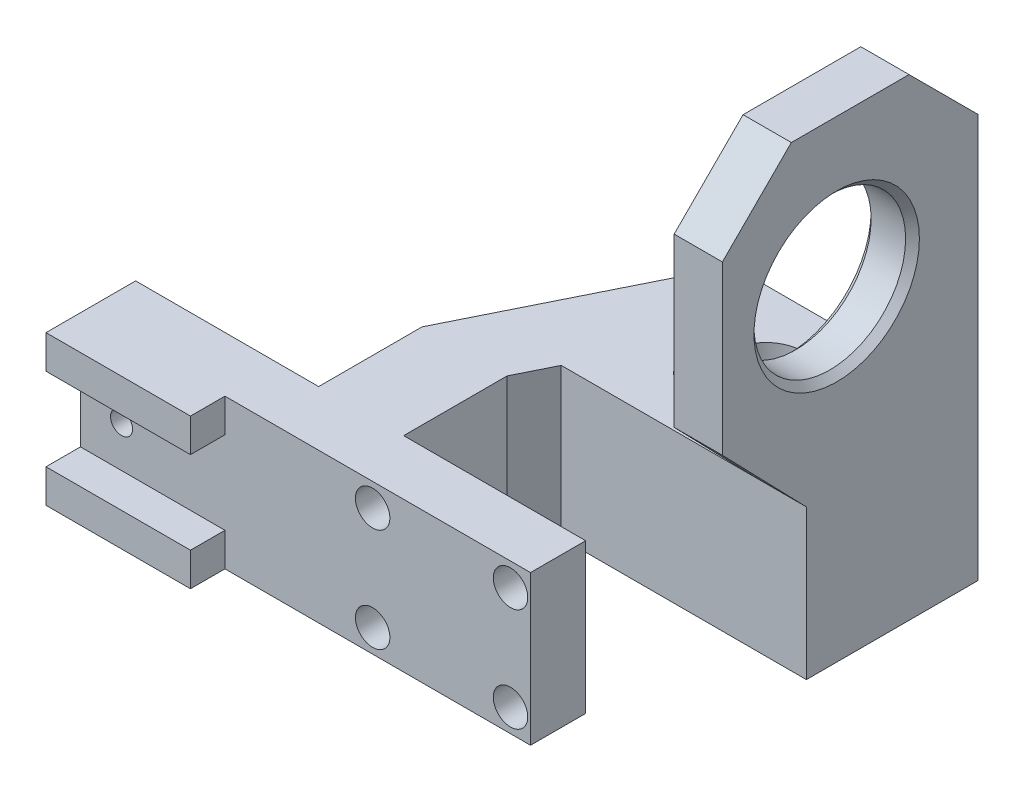
SolidWorks part; units mm, degrees
ref_plane "Přední rovina" through (0, 0, 0) normal (0, 0, 1) x (1, 0, 0)
ref_plane "Horní rovina" through (0, 0, 0) normal (0, 1, 0) x (1, 0, 0)
ref_plane "Pravá rovina" through (0, 0, 0) normal (1, 0, 0) x (0, 0, -1)
sketch "Skica1" plane through (0, 0, 0) normal (0, 0, 1) x (1, 0, 0)
  line L1 (16.212, -19.9414) -> (-34.0669, -19.9414)
  line L2 (16.212, -19.9414) -> (16.212, 1.7586)
  line L3 (16.212, 1.7586) -> (-34.0669, 1.7586)
  line L4 (-34.0669, -19.9414) -> (-34.0669, 1.7586)
  circle A0 centre (13.312, -16.5914) radius 1.6
  circle A1 centre (-6.688, -16.5914) radius 1.6
  circle A2 centre (-6.688, -1.5914) radius 1.6
  circle A3 centre (13.312, -1.5914) radius 1.6
  dimension "D1" = 3.2
  dimension "D2" = 2
  dimension "D3" = 2
extrude "Přidat vysunutím1" add sketch "Skica1" along normal blind 8
sketch "Skica2" plane through (0, 0, 8) normal (0, 0, 1) x (1, 0, 0)
  circle A0 centre (13.312, -16.5914) radius 2.5
  circle A1 centre (-6.688, -16.5914) radius 2.5
  circle A2 centre (-6.688, -1.5914) radius 2.5
  circle A3 centre (13.312, -1.5914) radius 2.5
  dimension "D1" = 5
  dimension "D2" = 2
  dimension "D3" = 2
extrude "Odebrat vysunutím1" cut sketch "Skica2" against normal blind 4
sketch "Skica4" plane through (0, 0, 0) normal (0, 0, -1) x (-1, 0, 0)
  line L0 (-16.212, 1.7586) -> (34.0669, 1.7586) construction
  line L1 (10.188, 1.7586) -> (22.5157, 1.7586)
  line L2 (10.188, 1.7586) -> (10.188, -19.9414)
  line L3 (10.188, -19.9414) -> (22.5157, -19.9414)
  line L4 (22.5157, 1.7586) -> (22.5157, -19.9414)
  line L5 (10.188, 1.7586) -> (10.188, -19.9414) construction
  line L6 (34.0669, -19.9414) -> (-16.212, -19.9414) construction
  line L7 (10.188, -19.9414) -> (10.188, 1.7586) construction
extrude "Přidat vysunutím2" add sketch "Skica4" along normal blind 15
sketch "Skica6" plane through (0, 1.7586, 0) normal (0, 1, 0) x (1, 0, 0)
  line L0 (-10.188, 15) -> (-22.5157, 15)
  line L1 (-10.188, 15) -> (-7.5858, 20.255)
  line L2 (-22.5157, 15) -> (-7.5858, 45.15)
  line L3 (4.7419, 45.15) -> (-7.5858, 45.15)
  line L5 (-7.5858, 45.15) -> (20.9737, 45.15)
  line L7 (-7.5858, 20.255) -> (20.9737, 20.255)
  line L8 (20.9737, 45.15) -> (20.9737, 20.255)
  circle A0 centre (8.2082, 34.15) radius 11 construction
  circle A3 centre (8.2082, 34.15) radius 5.4063
  line M11 (-10.188, 15) -> (-22.5157, 15)
extrude "Přidat vysunutím3" add sketch "Skica6" against normal up to surface (21.7 mm away) contours L8 L5 L3 L2 L1 L7 A3 M11 region at (1.476, 1.7586, -30.6172) up to face at (-12.6397, -19.9414, -1.75)
sketch "Skica7" plane through (0, -19.9414, 0) normal (0, -1, 0) x (1, 0, 0)
  line L0 (8.2082, -34.15) -> (0.2082, -34.15) construction
  line L1 (8.2082, -34.15) -> (2.5514, -28.4931) construction
  line L2 (8.2082, -34.15) -> (13.8651, -39.8069) construction
  circle A0 centre (8.2082, -34.15) radius 8 construction
  circle A1 centre (2.5514, -28.4931) radius 1.5
  circle A2 centre (13.8651, -39.8069) radius 1.5
  point P12 (8.2082, -34.15)
  dimension "D1" = 16
  dimension "D2" = 3
  dimension "D3" = 2
extrude "Odebrat vysunutím3" cut sketch "Skica7" against normal up to surface (21.7 mm away) up to face at (-6.1951, 1.7586, -12.0675)
sketch "Skica8" plane through (-34.0669, 0, 0) normal (-1, 0, 0) x (0, 0, 1)
  line L4 (0, 1.7586) -> (0, -19.9414)
  line L5 (0, -19.9414) -> (8, -19.9414)
  line L6 (8, -19.9414) -> (8, 1.7586)
  line L7 (8, 1.7586) -> (0, 1.7586)
  line L8 (0, 1.7586) -> (0, -19.9414)
  line L9 (0, -19.9414) -> (8, -19.9414)
  line L10 (8, -19.9414) -> (8, 1.7586)
  line L11 (8, 1.7586) -> (0, 1.7586)
  dimension "D1" = 0
extrude "Přidat vysunutím4" add sketch "Skica8" along normal blind 15
sketch "Skica9" plane through (0, 0, 8) normal (0, 0, 1) x (1, 0, 0)
  circle A0 centre (-43.1091, -9.0914) radius 1.6
  circle A1 centre (-243.1091, -9.0914) radius 1.6 construction
extrude "Odebrat vysunutím4" cut sketch "Skica9" against normal blind 15
sketch "Skica10" plane through (20.9737, 0, 0) normal (1, 0, 0) x (0, 0, -1)
  line L0 (8.0742, 14.3404) -> (20.255, 1.7586)
  line L1 (45.15, -19.9414) -> (20.255, -19.9414)
  line L2 (45.15, -19.9414) -> (45.15, 48.6222)
  line L3 (45.15, 48.6222) -> (8.0742, 48.6222)
  line L4 (8.0742, 14.3404) -> (8.0742, 48.6222)
  line L5 (20.255, 1.7586) -> (20.255, -19.9414)
  circle A0 centre (24.65, 27.2586) radius 11
  dimension "D1" = 22
extrude "Přidat vysunutím5" add sketch "Skica10" along normal blind 7
chamfer "Zkosení1" distance 10 angle 45 2 edges at (24.4737, 48.6222, -8.0742) (24.4737, 48.6222, -45.15)
sketch "Skica11" plane through (0, 0, 8) normal (0, 0, 1) x (1, 0, 0)
  line L0 (-49.0669, -19.9414) -> (16.212, -19.9414) construction
  line L1 (-28.1091, -3.0914) -> (-49.0669, -3.0914)
  line L3 (-28.1091, -15.0914) -> (-49.0669, -15.0914)
  line L7 (-49.0669, 1.7586) -> (-28.1091, 1.7586)
  line L8 (-49.0669, 1.7586) -> (-49.0669, -3.0914)
  line L9 (-49.0669, -19.9414) -> (-28.1091, -19.9414)
  line L10 (-28.1091, 1.7586) -> (-28.1091, -3.0914)
  line L11 (-28.1091, -15.0914) -> (-28.1091, -19.9414)
  line L12 (-49.0669, -15.0914) -> (-49.0669, -19.9414)
  point P0 (-43.1091, -9.0914)
extrude "Přidat vysunutím6" add sketch "Skica11" along normal blind 5
chamfer "Zkosení2" distance 1 angle 45 2 edges at (20.9737, 27.2586, -35.65) (27.9737, 27.2586, -35.65)
